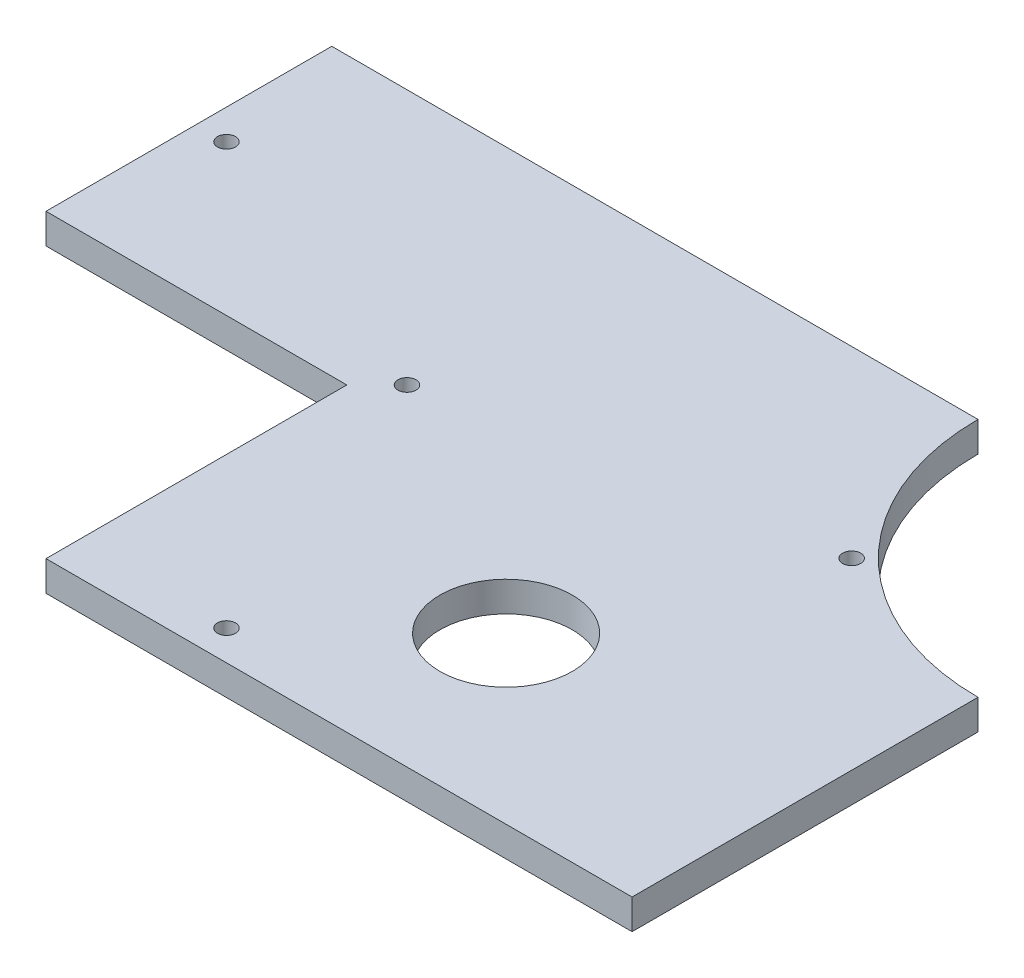
SolidWorks part; units mm, degrees
ref_plane "Plan de face" through (0, 0, 0) normal (0, 0, 1) x (1, 0, 0)
ref_plane "Plan de dessus" through (0, 0, 0) normal (0, 1, 0) x (1, 0, 0)
ref_plane "Plan de droite" through (0, 0, 0) normal (1, 0, 0) x (0, 0, -1)
sketch "Esquisse1" plane through (0, 0, 0) normal (0, 1, 0) x (1, 0, 0)
  line L1 (97.415, -97.5) -> (-97.415, -97.5)
  line L4 (-147.415, -47.5) -> (-147.415, 2.5)
  line L5 (-97.415, -47.5) -> (0, -47.5) construction
  line L6 (-48.7075, -47.5) -> (-48.1634, -92.5) construction
  line L9 (-147.415, 2.5) -> (-142.415, 2.5) construction
  line L14 (-147.415, -47.5) -> (-97.415, -47.5)
  line L15 (-97.415, -47.5) -> (-97.415, -97.5)
  line L16 (-92.415, -92.5) -> (-3.9118, -92.5) construction
  line L17 (-147.415, -42.5) -> (-92.415, -42.5) construction
  line L18 (-92.415, -42.5) -> (-92.415, -97.5) construction
  line L19 (0, 0) -> (-30.501, -30.501) construction
  line L20 (-147.415, 0) -> (0, 0)
  line L21 (0, -97.5) -> (0, 2.585)
  line L27 (-142.415, 2.5) -> (-142.415, -47.5) construction
  circle A3 centre (-142.415, -42.5) radius 1.5 construction
  circle A4 centre (-92.415, -42.5) radius 1.5
  circle A5 centre (-92.415, -92.5) radius 1.5 construction
  circle A14 centre (-142.415, -22.5) radius 1.5
  circle A15 centre (-72.415, -92.5) radius 1.5
  arc A16 (-40, 0) -> (0, -40) centre (0, 0) ccw
  circle A18 centre (-30.501, -30.501) radius 1.5
  circle A19 centre (-48.4354, -70) radius 11
  point P0 (0, 0)
  dimension "D7" = 20
  dimension "D2" = 3
  dimension "D12" = 40
  dimension "D14" = 22
  dimension "D3" = 45
  dimension "D4" = 5
  dimension "D5" = 5
  dimension "D6" = 5
  dimension "D8" = 20
  dimension "D9" = 5
  dimension "D10" = 50
  dimension "D11" = 194.83
  dimension "D13" = 45
  dimension "D15" = 5
extrude "Boss.-Extru.1" add sketch "Esquisse1" along normal blind 5 contours L14 L15 L1 L9 L4 A5 A4 A3 region at (-69.6739, 0, 46.0584)
